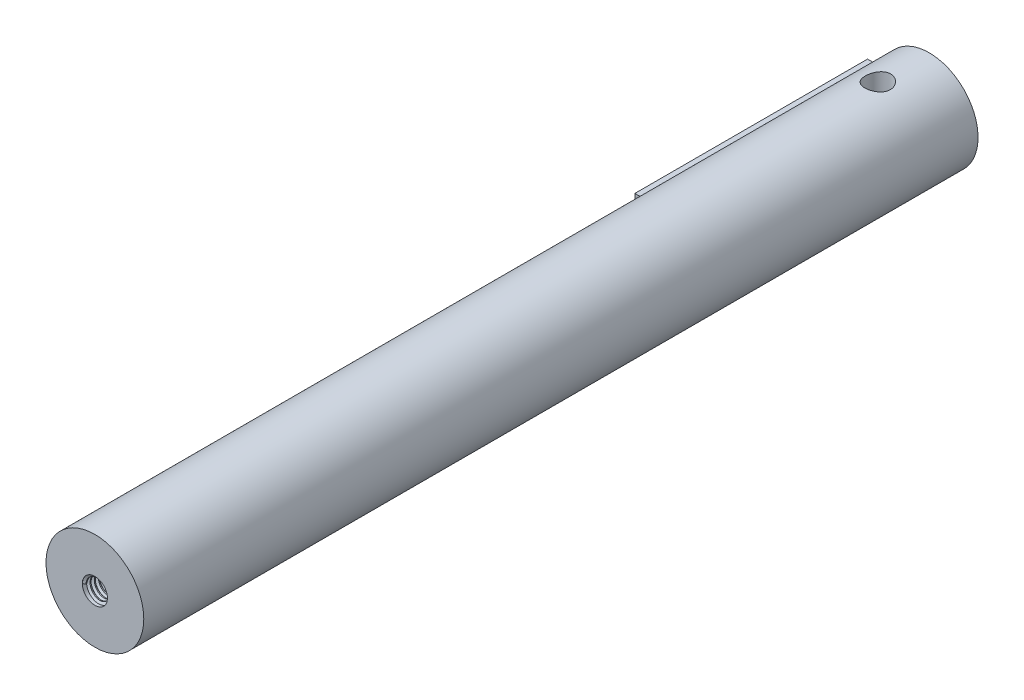
SolidWorks part; units mm, degrees
ref_plane "Front Plane" through (0, 0, 0) normal (0, 0, 1) x (1, 0, 0)
ref_plane "Top Plane" through (0, 0, 0) normal (0, 1, 0) x (1, 0, 0)
ref_plane "Right Plane" through (0, 0, 0) normal (1, 0, 0) x (0, 0, -1)
sketch "Sketch1" plane through (0, 0, 0) normal (0, 0, 1) x (1, 0, 0)
  line L0 (0, 0) -> (0, 3.175)
  line L1 (0, 3.175) -> (-15.621, 3.175)
  line L2 (-15.621, 3.175) -> (-15.621, -2.921)
  line L3 (-15.621, -2.921) -> (0, -2.921)
  line L4 (0, -2.921) -> (0, 0)
  circle A0 centre (0, 0) radius 12.3825
  dimension "D1" = 24.765
  dimension "D2" = 6.096
  dimension "D3" = 3.175
  dimension "D4" = 15.621
extrude "Boss-Extrude4" add sketch "Sketch1" along normal blind 58.928 contours L3 A0 L1 L0 L4 | L1 A0 L3 L4 L0 | A0 L1 L2 L3 region at (-6.1283, 0.1244, 0) region at (1.125, -0.0228, 0) region at (-13.9364, 0.1366, 0)
sketch "Sketch8" plane through (0, 0, 58.928) normal (0, 0, 1) x (1, 0, 0)
  circle A0 centre (0, 0) radius 12.3825
extrude "Boss-Extrude5" add sketch "Sketch8" along normal blind 152.4
sketch "Sketch10" plane through (0, 0, 211.328) normal (0, 0, 1) x (1, 0, 0)
  circle A0 centre (0, 0) radius 3.175
  dimension "D1" = 6.35
extrude "Cut-Extrude1" cut sketch "Sketch10" against normal blind 12.7
thread "Thread1" pitch 1.0583 method extrude profile "Thread Profile1" start angle 0, offset 0, length 0, pitch 1.0583, diameter 6.35
ref_plane "Plane1" through (-3.175, 0, 211.328) normal (0, -1, 0) x (-1, 0, 0)
sketch "Thread Profile1" plane through (-3.175, 0, 211.328) normal (0, -1, 0) x (-1, 0, 0)
  line L0 (0, 0) -> (0, 1.0583) construction
  line L11 (0, 0) -> (0, 0.926)
  line L12 (0, 0.926) -> (-0.5728, 0.5953)
  line L13 (-0.5728, 0.5953) -> (-0.5728, 0.3307)
  line L15 (-0.5728, 0.3307) -> (0, 0)
  line L17 (-0.5728, 0.463) -> (0, 0.463) construction
  point P2 (0, 0)
  dimension "Pitch" = 1.0583
  dimension "Profile_Angle" = 60
  dimension "Profile_Land" = 0.2646
  dimension "Profile_Height" = 0.5728
sketch "Sketch11" plane through (0, 0, 0) normal (0, 1, 0) x (1, 0, 0)
  line L0 (12.3825, 0) -> (-12.033, 0) construction
  line L1 (12.3825, -211.328) -> (12.3825, 0) construction
  circle A0 centre (-0.3175, -12.7) radius 3.175
  dimension "D1" = 6.35
  dimension "D2" = 12.7
  dimension "D3" = 12.7
extrude "Cut-Extrude2" cut sketch "Sketch11" against normal through all and the other way through all
